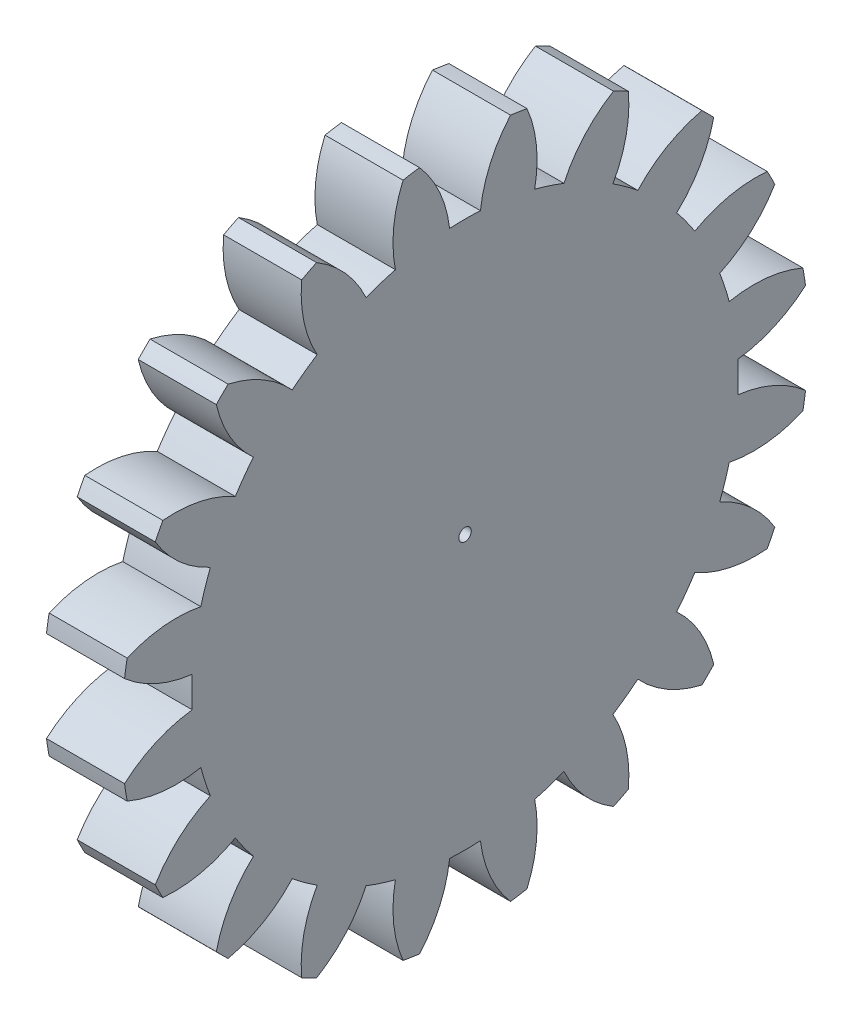
SolidWorks part; units mm, degrees
material "Delrin 2700 NC010, Low Viscosity Acetal Copolymer (SS)"
ref_plane "Plane1" through (0, 0, 0) normal (0, 0, 1) x (1, 0, 0)
ref_plane "Plane2" through (0, 0, 0) normal (0, 1, 0) x (1, 0, 0)
ref_plane "Plane3" through (0, 0, 0) normal (1, 0, 0) x (0, 0, -1)
sketch "HoldingSke" plane through (0, 0, 0) normal (0, 1, 0) x (1, 0, 0)
  line L0 (0, 0) -> (0.4698, -0.171)
  line L1 (-15, 0) -> (100, 0) construction
  line L2 (0, 0) -> (-2.1039, 2.3779)
  line L3 (0, 0) -> (-11.863, 4.5341)
  line L4 (0, 0) -> (8.1152, 2.9537)
  line L5 (0, 0) -> (-46.8476, -17.4728)
  line L6 (0, 0) -> (-4.1448, -2.7965)
  line L7 (-2.1039, 2.3779) -> (8.6586, 51.2059)
  line L8 (-76.2, 54.61) -> (-76.1, 54.61)
  line L9 (-71.009, 38.7566) -> (-53.1078, 45.2721)
  line L10 (-76.2, 71.12) -> (104.1128, 71.12)
  line L11 (0, 0) -> (-5, 0)
  line L12 (-76.2, 101.6) -> (-76.133, 101.6)
  line L13 (24.9733, 27.94) -> (52.9518, 28.4284)
  line L14 (24.9733, 27.94) -> (24.9743, 27.94)
  line L15 (24.9733, 27.94) -> (100.4006, 29.5858)
  line L16 (-63.627, -2) -> (-12.827, -2)
  circle A0 centre (0, 0) radius 0.4
  circle A1 centre (0, 0) radius 17.499
  circle A2 centre (0, 0) radius 37.5
  circle A3 centre (0, 0) radius 0.4
  dimension "Num_teeth" = 20
  dimension "Pitch_radius" = 180.3128
  dimension "Width" = 5
  dimension "Thickness" = 5
sketch "BasProSke" plane through (0, 0, 0) normal (0, 1, 0) x (1, 0, 0)
  line L0 (-10, 0) -> (60, 0) construction
  line L1 (0, 0) -> (0, 22)
  line L2 (0, 0) -> (5, 0)
  line L3 (5, 0) -> (5, 22)
  line L4 (5, 22) -> (0, 22)
  dimension "Thickness" = 5
  dimension "Diameter" = 44
revolve "Base-Revolve" add sketch "BasProSke" angle 360 about L0
sketch "TooCutSke" plane through (0, 0, 0) normal (1, 0, 0) x (0, 0, -1)
  line L1 (0, 0) -> (0, 107) construction
  line L2 (0, 0) -> (-1.6864, 19.9288) construction
  line L3 (0, 0) -> (-6.2409, 39.4033) construction
  line L4 (-1.6864, 19.9288) -> (-3.1204, 19.7016) construction
  arc A0 (0.9862, 17.4712) -> (-0.9862, 17.4712) centre (0, 0) ccw
  arc A1 (2.9329, 21.8293) -> (-2.9329, 21.8293) centre (0, 0) ccw
  circle A2 centre (0, 0) radius 20 construction
  circle A3 centre (0, 0) radius 18.7939 construction
  arc A4 (-0.9862, 17.4712) -> (-2.9329, 21.8293) centre (-8.9313, 16.536) ccw
  arc A5 (2.9329, 21.8293) -> (0.9862, 17.4712) centre (8.9313, 16.536) ccw
extrude "ToothCut" cut sketch "TooCutSke" along normal through all
fillet "Breaks" [suppressed] radius 0.04 tangent propagation no
fillet "RootFillets" [suppressed] radius 0.501
pattern_circular "TeethCuts" count 20 every 18 about axis through (-10, 0, 0) along (1, 0, 0) of "ToothCut", "RootFillets", "Breaks"
sketch "HubNeaOneSke" plane through (0, 0, 0) normal (-1, 0, 0) x (0, 0, 1)
  circle A0 centre (0, 0) radius 17.499
  dimension "Diameter" = 34.998
extrude "HubNearOne" [suppressed] add sketch "HubNeaOneSke" along normal blind 45.0001
sketch "HubNeaBotSke" plane through (0, 0, 0) normal (-1, 0, 0) x (0, 0, 1)
  circle A0 centre (0, 0) radius 17.499
  dimension "Diameter" = 34.998
extrude "HubNearBoth" [suppressed] add sketch "HubNeaBotSke" along normal blind 22.5
ref_plane "FarPln" through (5, 0, 0) normal (1, 0, 0) x (0, 0, -1)
sketch "HubFarSke" plane through (5, 0, 0) normal (1, 0, 0) x (0, 0, -1)
  circle A0 centre (0, 0) radius 17.499
  dimension "Diameter" = 34.998
extrude "HubFar" [suppressed] add sketch "HubFarSke" along normal blind 22.5
sketch "BorSke" plane through (0, 0, 0) normal (1, 0, 0) x (0, 0, -1)
  circle A0 centre (0, 0) radius 0.4
  dimension "Diameter" = 0.8
extrude "Bore" cut sketch "BorSke" along normal mid plane 100.0001
sketch "KeySke" plane through (0, 0, 0) normal (1, 0, 0) x (0, 0, -1)
  line L0 (-0.05, 0) -> (-0.05, 0.5)
  line L1 (-0.05, 0.5) -> (0.05, 0.5)
  line L2 (0.05, 0.5) -> (0.05, 0)
  line L3 (0, 0) -> (0, 34) construction
  line L4 (-0.05, 0) -> (0.05, 0)
  dimension "Width" = 0.1
extrude "Keyway" [suppressed] cut sketch "KeySke" along normal mid plane 100.0001
pattern_circular "Keyway2" [suppressed] count 2 every 90 about axis through (-10, 0, 0) along (1, 0, 0) reverse direction yes
equation "' \"Module@HoldingSke\" = 6.35"
equation "' \"Num_teeth@HoldingSke\" = 12"
equation "' \"Ap@HoldingSke\" =  20"
equation "' \"Ap@HoldingSke\" = 20"
equation "' \"Width@HoldingSke\" = 0.5 * 25.4"
equation "' \"Hub_dia@HoldingSke\"= 1 * 25.4"
equation "' \"Hub_dia@HoldingSke\" = 1 * 25.4"
equation "' \"Overall_len@HoldingSke\" = 1.0 * 25.4"
equation "' \"Bore@HoldingSke\" = 0.75 * 25.4"
equation "' \"T_dim@HoldingSke\" = 0.1 * 25.4"
equation "' \"Width@KeySke\" = 0.25 * 25.4"
equation "' \"Show_teeth@HoldingSke\" = 13"
equation "' \"Backlash@HoldingSke\" = 0.009 * 25.4"
equation "' \"Addendum_fac@HoldingSke\" = 1.0"
equation "' \"Dedendum_fac@HoldingSke\" = 1.25"
equation "' \"Dedendum_add@HoldingSke\" = 0.00005 * 25.4"
equation "' \"Clearance_fac@HoldingSke\" = 0.25"
equation "\"Pitch@HoldingSke\" = 1 / \"Module@HoldingSke\""
equation "\"Overcut_dia@TooCutSke\" = (\"Num_teeth@HoldingSke\" + 2 * \"Addendum_fac@HoldingSke\") / \"Pitch@HoldingSke\" + 0.002 * 25.4"
equation "\"Pitch_dia@TooCutSke\" = \"Num_teeth@HoldingSke\" / \"Pitch@HoldingSke\""
equation "\"Base_dia@TooCutSke\" = \"Num_teeth@HoldingSke\" / \"Pitch@HoldingSke\" * cos((\"Ap@HoldingSke\"  * 3.14159265 / 180))"
equation "\"Root_dia@TooCutSke\" = (\"Num_teeth@HoldingSke\" + 2) / \"Pitch@HoldingSke\" - 2 * (\"Addendum_fac@HoldingSke\" + \"Dedendum_fac@HoldingSke\") / \"Pitch@HoldingSke\" - \"Dedendum_add@HoldingSke\" * 2"
equation "\"Half_ang@TooCutSke\" = 180 / \"Num_teeth@HoldingSke\""
equation "\"Half_CT@TooCutSke\" = \"Num_teeth@HoldingSke\" / \"Pitch@HoldingSke\" * sin((3.14159265 / 2 / \"Num_teeth@HoldingSke\")) / 2 - 7 * \"Backlash@HoldingSke\" / 4"
equation "\"Flank_rad@TooCutSke\" = \"Num_teeth@HoldingSke\" / \"Pitch@HoldingSke\" / 5"
equation "\"Radius@RootFillets\" = \"Clearance_fac@HoldingSke\" / \"Pitch@HoldingSke\" + \"Dedendum_add@HoldingSke\""
equation "\"Break_rad@Breaks\" = 0.02 / \"Pitch@HoldingSke\""
equation "\"Thickness@HoldingSke\" = \"Width@HoldingSke\""
equation "\"OAL@HoldingSke\" = \"Thickness@HoldingSke\""
equation "\"MHD@HoldingSke\" = (\"Num_teeth@HoldingSke\" + 2) / \"Pitch@HoldingSke\" - 2 * (\"Addendum_fac@HoldingSke\" + \"Dedendum_fac@HoldingSke\")  / \"Pitch@HoldingSke\" - \"Dedendum_add@HoldingSke\" * 2"
equation "\"MBD@HoldingSke\" = (\"Num_teeth@HoldingSke\" + 2) / \"Pitch@HoldingSke\" - 2 * (\"Addendum_fac@HoldingSke\" + \"Dedendum_fac@HoldingSke\")  / \"Pitch@HoldingSke\" - \"Dedendum_add@HoldingSke\" * 2 - 0.002 * 25.4"
equation "\"MHD@HoldingSke\" = ((sgn( \"MHD@HoldingSke\" - \"Hub_dia@HoldingSke\" )-1)*( \"MHD@HoldingSke\" - \"Hub_dia@HoldingSke\" ))/-2+ \"Hub_dia@HoldingSke\""
equation "\"MBD@HoldingSke\" = ((sgn( \"MBD@HoldingSke\" - \"Bore@HoldingSke\" )-1)*( \"MBD@HoldingSke\" - \"Bore@HoldingSke\" ))/-2+ \"Bore@HoldingSke\""
equation "\"OAL@HoldingSke\" = ((sgn( \"OAL@HoldingSke\" - \"Overall_len@HoldingSke\" )+1)*( \"OAL@HoldingSke\" - \"Overall_len@HoldingSke\" ))/2 + \"Overall_len@HoldingSke\" + 0.000002 * 25.4"
equation "\"Num_teeth@TeethCuts\" = int( \"Show_teeth@HoldingSke\" ) + 1"
equation "\"Num_teeth@TeethCuts\" = ((sgn( \"Num_teeth@TeethCuts\" - \"Num_teeth@HoldingSke\" )-1)*( \"Num_teeth@TeethCuts\" - \"Num_teeth@HoldingSke\" ))/-2+ \"Num_teeth@HoldingSke\""
equation "\"Num_teeth@TeethCuts\" = ((sgn( \"Num_teeth@TeethCuts\" - 2.0)+1)*( \"Num_teeth@TeethCuts\" - 2.0))/2 +2.0"
equation "\"Angle@TeethCuts\" = 360.0 / \"Num_teeth@HoldingSke\""
equation "\"Diameter@BasProSke\" = (\"Num_teeth@HoldingSke\" + 2 * \"Addendum_fac@HoldingSke\") / \"Pitch@HoldingSke\""
equation "\"Thickness@BasProSke\"  = \"Thickness@HoldingSke\""
equation "' \"Fillet_rad@BasProSke\" =  \"Thickness@HoldingSke\" * 0.05"
equation "' \"Fillet_rad@BasProSke\" = \"Thickness@HoldingSke\" * 0.05"
equation "\"MHD@HoldingSke\" = ((sgn( \"MHD@HoldingSke\" - \"Root_dia@TooCutSke\" )-1)*( \"MHD@HoldingSke\" - \"Root_dia@TooCutSke\" ))/-2+ \"Root_dia@TooCutSke\""
equation "\"Diameter@HubNeaOneSke\" = \"MHD@HoldingSke\""
equation "\"Length@HubNearOne\" = \"OAL@HoldingSke\" - \"Thickness@BasProSke\""
equation "\"Diameter@HubNeaBotSke\" = \"MHD@HoldingSke\""
equation "\"Length@HubNearBoth\" = ( \"OAL@HoldingSke\" - \"Thickness@BasProSke\" ) / 2.0"
equation "\"Thickness@FarPln\" = \"Thickness@BasProSke\""
equation "\"Diameter@HubFarSke\" = \"MHD@HoldingSke\""
equation "\"Length@HubFar\" = ( \"OAL@HoldingSke\" - \"Thickness@BasProSke\" ) / 2.0"
equation "\"Diameter@BorSke\" = \"MBD@HoldingSke\""
equation "\"D1@Bore\" = \"OAL@HoldingSke\" * 2.0"
equation "\"D1@Keyway\" = \"OAL@HoldingSke\" * 2.0"
equation "\"Offset@KeySke\" = \"T_dim@HoldingSke\" + \"MBD@HoldingSke\" / 2.0"
